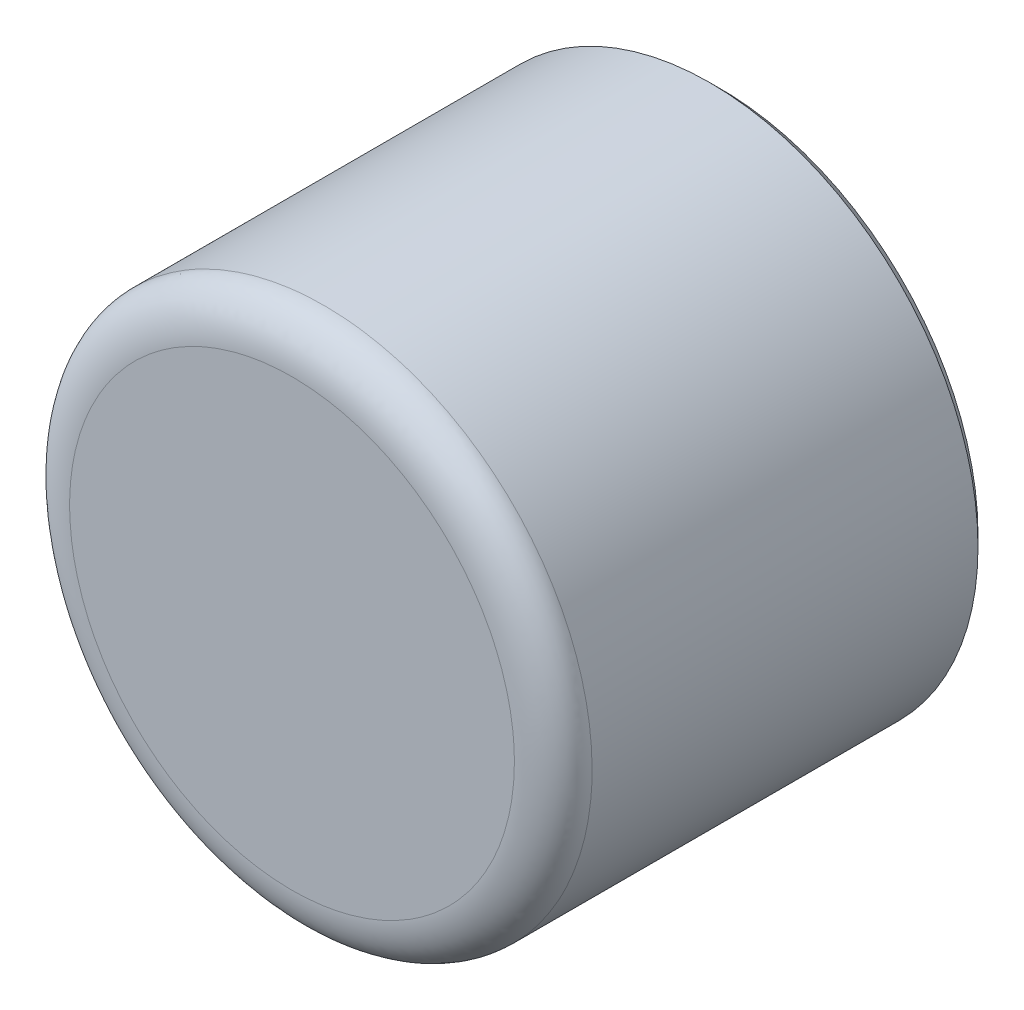
SolidWorks part; units mm, degrees
ref_plane "Спереди" through (0, 0, 0) normal (0, 0, 1) x (1, 0, 0)
ref_plane "Сверху" through (0, 0, 0) normal (0, 1, 0) x (1, 0, 0)
ref_plane "Справа" through (0, 0, 0) normal (1, 0, 0) x (0, 0, -1)
sketch "Эскиз1" plane through (0, 0, 0) normal (0, 0, 1) x (1, 0, 0)
  circle A0 centre (0, 0) radius 10
  dimension "D1" = 20
extrude "Бобышка-Вытянуть1" add sketch "Эскиз1" along normal blind 16
fillet "Скругление1" radius 1.7 1 edges at (10, 0, 16)
sketch "Эскиз2" plane through (0, 0, 0) normal (0, 0, -1) x (-1, 0, 0)
  circle A0 centre (0, 0) radius 3.15
  dimension "D1" = 6.3
extrude "Вырез-Вытянуть1" cut sketch "Эскиз2" against normal blind 11
sketch "Эскиз3" plane through (0, 0, 0) normal (0, 0, -1) x (-1, 0, 0)
  line L0 (-0.5, 3.15) -> (0, 2.65)
  line L1 (-0.5, 3.15) -> (0, 3.65)
  line L2 (0, 2.65) -> (0.5, 3.15)
  line L3 (0, 3.65) -> (0.5, 3.15)
  line L4 (-0.5, 3.15) -> (0.5, 3.15) construction
  line L5 (0, 2.65) -> (0, 3.65) construction
  circle A0 centre (0, 0) radius 3.15 construction
  point P1 (0, 3.15)
  dimension "D1" = 0.5
extrude "Бобышка-Вытянуть2" add sketch "Эскиз3" against normal up to next
pattern_circular "Круговой массив1" count 18 over 360 about axis through (0, 0, 0) along (0, 0, 1) of "Бобышка-Вытянуть2"
sketch "Эскиз4" plane through (0, 0, 0) normal (0, 0, -1) x (-1, 0, 0)
  circle A0 centre (0, 0) radius 4.5
  circle A1 centre (0, 0) radius 8.5
  dimension "D1" = 9
  dimension "D2" = 17
extrude "Вырез-Вытянуть2" cut sketch "Эскиз4" against normal blind 14
fillet "Скругление2" radius 2 2 edges at (-8.5, 0, 14) (-4.5, 0, 14)
chamfer "Фаска1" distance 0.4 angle 45 2 edges at (10, 0, 0) (-8.5, 0, 0)
chamfer "Фаска2" distance 0.4 angle 45 55 edges at (2.0312, -2.0587, 0) (1.6747, -2.3579, 0) (0.547, -3.1021, 0) (1.2046, -2.6293, 0) (0.7673, -2.7885, 0) (-0.547, -3.1021, 0) (0.2327, -2.8827, 0) (-0.2327, -2.8827, 0) (-1.575, -2.728, 0) (-0.7673, -2.7885, 0) (-1.2046, -2.6293, 0) (-2.413, -2.0248, 0) (-1.6747, -2.3579, 0) (-2.0312, -2.0587, 0) (-2.96, -1.0774, 0) (-2.3801, -1.6429, 0) (-2.6129, -1.2398, 0) (-3.15, 0, 0) (-2.7985, -0.7298, 0) (-2.8793, -0.2714, 0) (-2.96, 1.0774, 0) (-2.8793, 0.2714, 0) (-2.7985, 0.7298, 0) (-2.413, 2.0248, 0) (-2.6129, 1.2398, 0) (-2.3801, 1.6429, 0) (-1.575, 2.728, 0) (-2.0312, 2.0587, 0) (-1.6747, 2.3579, 0) (0.547, 3.1021, 0) (-0.547, 3.1021, 0) (-1.2046, 2.6293, 0) (-0.7673, 2.7885, 0) (0.2327, 2.8827, 0) (-0.2327, 2.8827, 0) (-4.5, 0, 0) (1.575, 2.728, 0) (0.7673, 2.7885, 0) (1.2046, 2.6293, 0) (2.413, 2.0248, 0) (1.6747, 2.3579, 0) (2.0312, 2.0587, 0) (2.96, 1.0774, 0) (2.3801, 1.6429, 0) (2.6129, 1.2398, 0) (3.15, 0, 0) (2.7985, 0.7298, 0) (2.8793, 0.2714, 0) (2.96, -1.0774, 0) (2.8793, -0.2714, 0) (2.7985, -0.7298, 0) (2.413, -2.0248, 0) (2.6129, -1.2398, 0) (2.3801, -1.6429, 0) (1.575, -2.728, 0)
